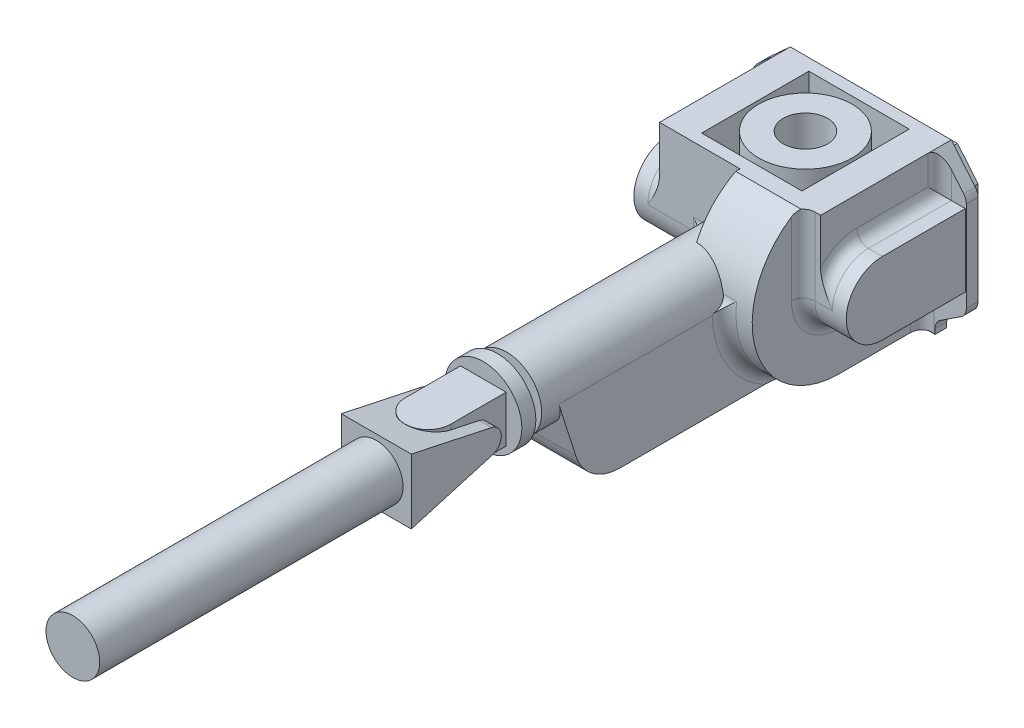
SolidWorks part; units mm, degrees
ref_plane "Front Plane" through (0, 0, 0) normal (0, 0, 1) x (1, 0, 0)
ref_plane "Top Plane" through (0, 0, 0) normal (0, 1, 0) x (1, 0, 0)
ref_plane "Right Plane" through (0, 0, 0) normal (1, 0, 0) x (0, 0, -1)
sketch "Sketch1" plane through (0, 0, 0) normal (0, 1, 0) x (1, 0, 0)
  line L1 (-3.45, -2.8) -> (3.45, -2.8)
  line L2 (-3.45, -2.8) -> (-3.45, 2.8)
  line L3 (-3.45, 2.8) -> (3.45, 2.8)
  line L4 (3.45, -2.8) -> (3.45, 2.8)
  line L5 (-3.45, -2.8) -> (3.45, 2.8) construction
  line L6 (-3.45, 2.8) -> (3.45, -2.8) construction
  point P0 (0, 0)
  dimension "D1" = 5.6
  dimension "D2" = 6.9
extrude "Boss-Extrude1" add sketch "Sketch1" along normal blind 3.3
sketch "Sketch2" plane through (3.45, 0, 0) normal (1, 0, 0) x (0, 0, -1)
  line L0 (-2.8, 0) -> (2.8, 0) construction
  line L1 (-2.8, 3.3) -> (-2.8, 0) construction
  line L2 (-1.25, 1.55) -> (2.8, 1.55)
  line L3 (2.8, 3.3) -> (2.8, 0) construction
  line L4 (-1.25, -1.55) -> (2.8, -1.55)
  line L5 (2.8, -1.55) -> (2.8, 1.55)
  arc A0 (-1.25, 1.55) -> (-1.25, -1.55) centre (-1.25, 0) ccw
  dimension "D1" = 3.1
extrude "Boss-Extrude2" add sketch "Sketch2" along normal blind 1.1 and the other way blind 8 separate body
sketch "Sketch3" plane through (0, 0, 0) normal (1, 0, 0) x (0, 0, -1)
  line L0 (-1.25, -3.73) -> (2.7899, -3.73)
  line L1 (2.7899, -3.73) -> (2.8, 3.3)
  line L2 (2.8, 3.3) -> (-2.9886, 3.3)
  arc A0 (-2.9886, 3.3) -> (-1.25, -3.73) centre (-1.25, 0) ccw
  dimension "D1" = 7.46
extrude "Boss-Extrude3" add sketch "Sketch3" along normal blind 2.7
sketch "Sketch5" plane through (0, 0, 0) normal (-1, 0, 0) x (0, 0, 1)
  line L0 (-2.7899, -3.73) -> (10.8977, -3.73)
  line L1 (10.8977, -3.73) -> (12.0845, 0.0129)
  line L2 (12.0845, 0.0129) -> (-2.7962, 0.0129)
  line L3 (-2.7962, 0.0129) -> (-2.7899, -3.73)
extrude "Boss-Extrude4" add sketch "Sketch5" along normal blind 1.5 and the other way blind 1.5
sketch "Sketch6" plane through (0, 0, -2.8) normal (0, 0, -1) x (-1, 0, 0)
  line L0 (0, 3.3) -> (3.45, 3.3)
  line L1 (-3.45, 3.3) -> (3.45, 3.3) construction
  line L2 (3.45, 3.3) -> (4.3624, 2.4668)
  line L3 (4.5252, 2.0976) -> (4.5252, -2.1189)
  line L4 (4.2791, -2.5497) -> (3.4747, -3.0238)
  line L5 (3.2286, -3.4545) -> (3.2286, -3.7699)
  line L6 (3.2286, -3.7699) -> (-3.2544, -3.7699)
  line L7 (-3.2544, -3.7699) -> (-3.2544, -3.5509)
  line L8 (-3.4807, -3.1325) -> (-4.3675, -2.5526)
  line L9 (-4.5939, -2.1341) -> (-4.5939, 1.7425)
  line L10 (-4.4785, 2.062) -> (-3.45, 3.3)
  line L11 (-3.45, 3.3) -> (0, 3.3)
  line L12 (3.45, 3.3) -> (3.45, 1.55) construction
  arc A0 (4.3624, 2.4668) -> (4.5252, 2.0976) centre (4.0252, 2.0976) cw
  arc A1 (4.5252, -2.1189) -> (4.2791, -2.5497) centre (4.0252, -2.1189) cw
  arc A2 (3.4747, -3.0238) -> (3.2286, -3.4545) centre (3.7286, -3.4545) ccw
  arc A3 (-3.2544, -3.5509) -> (-3.4807, -3.1325) centre (-3.7544, -3.5509) ccw
  arc A4 (-4.3675, -2.5526) -> (-4.5939, -2.1341) centre (-4.0939, -2.1341) cw
  arc A5 (-4.5939, 1.7425) -> (-4.4785, 2.062) centre (-4.0939, 1.7425) cw
  dimension "D1" = 0.5
extrude "Boss-Extrude5" add sketch "Sketch6" against normal blind 0.5
fillet "Fillet1" radius 2 1 edges at (0, -3.73, 10.8977)
fillet "Fillet2" radius 0.5 19 edges at (3.45, 1.55, -0.525) (2.7, 1.65, 2.8) (2.7, -1.096, 2.346) (-3.45, 1.096, 2.346) (-1.5, 0.0065, 2.8) (-1.5, -1.096, 2.346) (3.45, 2.425, -2.3) (-3.45, 2.425, -2.3) (3.45, 1.096, 2.346) (2.7, -1.55, -0.525) (2.7, -2.64, -2.3) (1.5, -2.6329, 3.8921) (0, 0.0129, 3.89) (0.75, 0.0129, 4.98) (-0.75, 0.0129, 2.8) (-3.45, 1.55, -0.525) (-3.0126, -1.55, -2.3) (-1.5, -1.55, -0.525) (-1.5, -2.64, -2.3)
sketch "Sketch7" plane through (0, 0, -2.8) normal (0, 0, -1) x (-1, 0, 0)
  line L28 (4.0252, -2.1189) -> (4.0252, -1.05)
  line L29 (4.0252, -1.05) -> (4.05, -1.05)
  line L30 (4.05, -1.05) -> (4.05, 1.05)
  line L31 (4.05, 1.05) -> (4.0252, 1.05)
  line L32 (4.0252, 1.05) -> (4.0252, 2.0976)
  line L33 (4.0252, 2.0976) -> (3.256, 2.8)
  line L34 (3.256, 2.8) -> (-3.2154, 2.8)
  line L35 (-3.2154, 2.8) -> (-4.0939, 1.7425)
  line L36 (-4.0939, 1.7425) -> (-4.0939, -2.1341)
  line L37 (-4.0939, -2.1341) -> (-3.2071, -2.714)
  line L38 (-2.7947, -3.2699) -> (2.7458, -3.2699)
  line L39 (3.2208, -2.593) -> (4.0252, -2.1189)
  line L40 (4.0252, -2.1189) -> (4.0252, -1.05)
  line L41 (4.0252, -1.05) -> (4.05, -1.05)
  line L42 (4.05, -1.05) -> (4.05, 1.05)
  line L43 (4.05, 1.05) -> (4.0252, 1.05)
  line L44 (4.0252, 1.05) -> (4.0252, 2.0976)
  line L45 (4.0252, 2.0976) -> (3.256, 2.8)
  line L46 (3.256, 2.8) -> (-3.2154, 2.8)
  line L47 (-3.2154, 2.8) -> (-4.0939, 1.7425)
  line L48 (-4.0939, 1.7425) -> (-4.0939, -2.1341)
  line L49 (-4.0939, -2.1341) -> (-3.2071, -2.714)
  line L50 (-2.7947, -3.2699) -> (2.7458, -3.2699)
  line L51 (3.2208, -2.593) -> (4.0252, -2.1189)
  arc A12 (-2.7947, -3.2699) -> (-3.2071, -2.714) centre (-3.7544, -3.5509) ccw
  arc A13 (3.2208, -2.593) -> (2.7458, -3.2699) centre (3.7286, -3.4545) ccw
  arc A14 (-2.7947, -3.2699) -> (-3.2071, -2.714) centre (-3.7544, -3.5509) ccw
  arc A15 (3.2208, -2.593) -> (2.7458, -3.2699) centre (3.7286, -3.4545) ccw
  dimension "D1" = 0.5
extrude "Boss-Extrude6" add sketch "Sketch7" along normal blind 0.5
sketch "Sketch8" plane through (0, 3.3, 0) normal (0, 1, 0) x (1, 0, 0)
  line L1 (-2.15, 2.2967) -> (2.15, 2.2967)
  line L2 (-2.15, 2.2967) -> (-2.15, -2.2967)
  line L3 (-2.15, -2.2967) -> (2.15, -2.2967)
  line L4 (2.15, 2.2967) -> (2.15, -2.2967)
  line L5 (-2.15, 2.2967) -> (2.15, -2.2967) construction
  line L6 (-2.15, -2.2967) -> (2.15, 2.2967) construction
  point P0 (0, 0)
  dimension "D1" = 4.3
extrude "Cut-Extrude1" cut sketch "Sketch8" against normal blind 4.3
sketch "Sketch9" plane through (0, 3.3, 0) normal (0, 1, 0) x (1, 0, 0)
  circle A0 centre (0, 0) radius 0.95
  circle A1 centre (0, 0) radius 2
  dimension "D1" = 4
  dimension "D2" = 1.9
extrude "Boss-Extrude7" add sketch "Sketch9" against normal blind 4.3
sketch "Sketch12" plane through (0, 0, 2.8) normal (0, 0, 1) x (1, 0, 0)
  circle A0 centre (0, 0) radius 1.501
extrude "Boss-Extrude8" add sketch "Sketch12" along normal blind 10
sketch "Sketch13" plane through (0, 0, 12.8) normal (0, 0, 1) x (1, 0, 0)
  circle A0 centre (0, 0) radius 0.7974
extrude "Boss-Extrude9" add sketch "Sketch13" along normal blind 0.4
sketch "Sketch14" plane through (0, 0, 13.2) normal (0, 0, 1) x (1, 0, 0)
  circle A0 centre (0, 0) radius 1.65
  dimension "D1" = 3.3
extrude "Boss-Extrude10" add sketch "Sketch14" along normal blind 0.6
sketch "Sketch16" plane through (0, 0, 0) normal (0, 1, 0) x (1, 0, 0)
  line L0 (0, -13.8) -> (0, -16.687) construction
  line L1 (-1.65, -13.8) -> (1.65, -13.8) construction
  line L2 (0.9756, -16.1712) -> (0.9756, -13.8)
  line L3 (0.9756, -13.8) -> (-0.9756, -13.8)
  line L4 (-0.9756, -13.8) -> (-0.9756, -16.1712)
  arc A1 (-0.9756, -16.1712) -> (0.9756, -16.1712) centre (0, -16.1712) ccw
extrude "Boss-Extrude11" add sketch "Sketch16" along normal blind 1 and the other way blind 1
sketch "Sketch17" plane through (0, 0, 0) normal (1, 0, 0) x (0, 0, -1)
  line L0 (-18.3876, 1.2568) -> (-18.3876, -1.5215)
  line L3 (-18.3876, 1.2568) -> (-14.9534, 0.5246)
  line L4 (-18.3876, -1.5215) -> (-14.916, -0.5152)
  arc A1 (-14.916, -0.5152) -> (-14.9534, 0.5246) centre (-15.0653, 0) ccw
extrude "Boss-Extrude12" add sketch "Sketch17" along normal blind 1.5 and the other way blind 1.5
sketch "Sketch18" plane through (0, 0, 18.3876) normal (0, 0, 1) x (1, 0, 0)
  circle A0 centre (0, -0.1323) radius 1.15
  dimension "D1" = 2.3
extrude "Boss-Extrude13" add sketch "Sketch18" along normal blind 13
